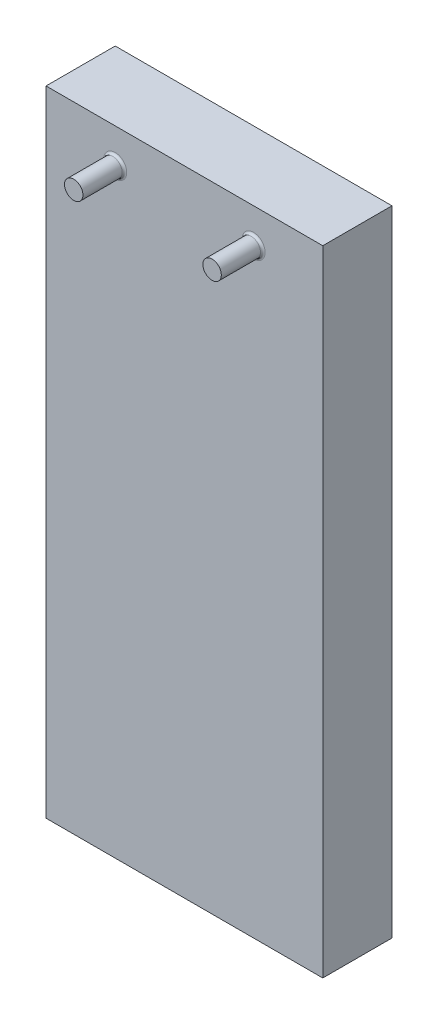
SolidWorks part; units mm, degrees
ref_plane "Front Plane" through (0, 0, 0) normal (0, 0, 1) x (1, 0, 0)
ref_plane "Top Plane" through (0, 0, 0) normal (0, 1, 0) x (1, 0, 0)
ref_plane "Right Plane" through (0, 0, 0) normal (1, 0, 0) x (0, 0, -1)
sketch "Sketch1" plane through (0, 0, 0) normal (0, 1, 0) x (1, 0, 0)
  line L1 (-60, -15) -> (60, -15)
  line L2 (-60, -15) -> (-60, 15)
  line L3 (-60, 15) -> (60, 15)
  line L4 (60, -15) -> (60, 15)
  line L5 (-60, -15) -> (60, 15) construction
  line L6 (-60, 15) -> (60, -15) construction
  point P0 (0, 0)
  dimension "D1" = 120
  dimension "D2" = 30
extrude "Boss-Extrude1" add sketch "Sketch1" along normal blind 275
sketch "Sketch2" plane through (0, 0, 15) normal (0, 0, 1) x (1, 0, 0)
  line L0 (-60, 245) -> (60, 245)
  line L1 (-60, 275) -> (-60, 0) construction
  line L2 (60, 275) -> (60, 0) construction
  line L3 (-60, 275) -> (60, 275) construction
  line L4 (-60, 245) -> (-60, 275)
  line L5 (-60, 260) -> (60, 260) construction
  circle A2 centre (-30, 260) radius 4
  circle A3 centre (30, 260) radius 4
  dimension "D4" = 8
  dimension "D1" = 30
  dimension "D2" = 30
  dimension "D3" = 30
extrude "Boss-Extrude2" add sketch "Sketch2" along normal blind 18 contours L5 A3 | A3 L5 | L5 A2 | A2 L5 region at (-30, 261.6977, 15) region at (30, 261.6977, 15) region at (30, 258.3023, 15) region at (-30, 258.3023, 15)
fillet "Fillet1" radius 1 2 edges at (26, 260, 15) (-34, 260, 15)
equation "\"PCWidth\"= 340mm'Distance of longest part parallel to GPU(ussually GPU)"
equation "\"PCLength\"= 145mm'Length across I/O from PS to GPU"
equation "\"PCHeight\"= 180mm'Tallest point with mobo laying flat"
equation "\"WallThickness\"= 9mm'Thickness of each outer tank wall"
equation "\"ThermoBarrierThickness\"= 6mm'Thickness of barrier between hot side and cold side"
equation "\"HotSideGap\"= 36mm'Space in the hot side for a pump"
equation "\"PCClearance\"= 40mm'Clearance from top of tank to top of PC"
equation "\"RadiatorHeight\"= 275mm'Final Height from ground of radiators"
equation "\"D1@Boss-Extrude1\"=\"RadiatorHeight\""
